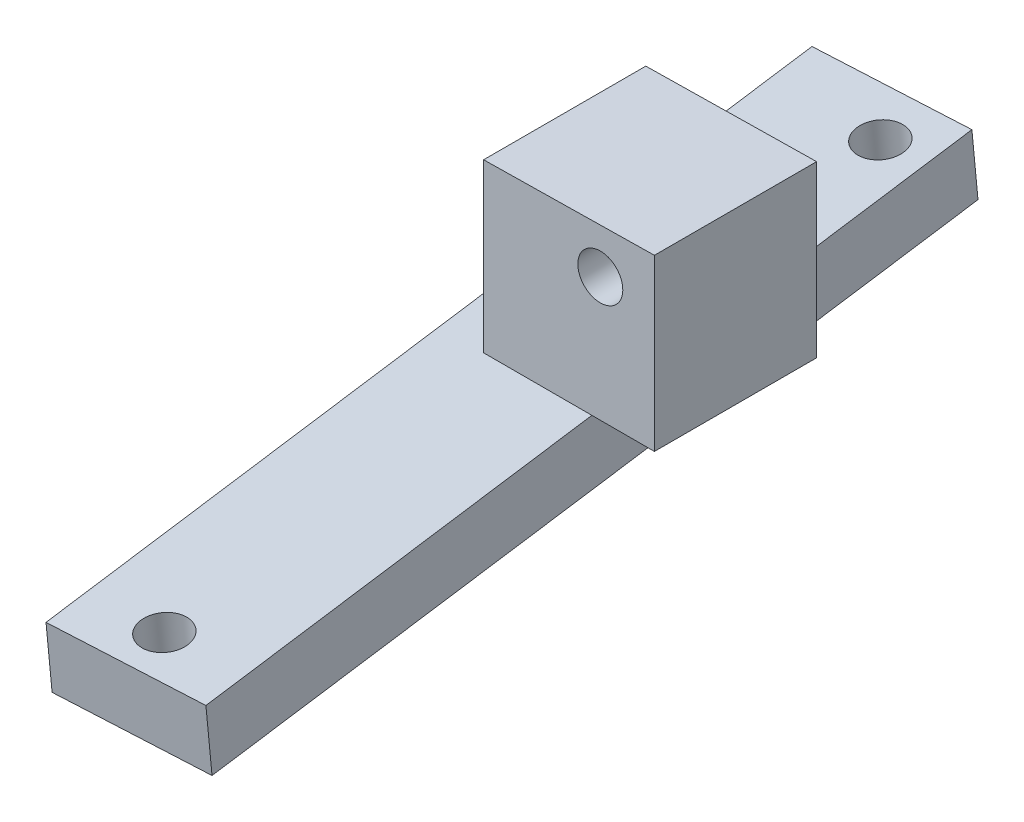
SolidWorks part; units mm, degrees
ref_plane "Front Plane" through (0, 0, 0) normal (0, 0, 1) x (1, 0, 0)
ref_plane "Top Plane" through (0, 0, 0) normal (0, 1, 0) x (1, 0, 0)
ref_plane "Right Plane" through (0, 0, 0) normal (1, 0, 0) x (0, 0, -1)
sketch "Sketch1" plane through (0, 0, 0) normal (0, 0, 1) x (1, 0, 0)
  line L4 (-277.3561, 264.2791) -> (-301.4861, 263.9)
  line L5 (-301.4861, 263.9) -> (-301.4861, 241.3438)
  line L6 (-301.4861, 241.3438) -> (-277.3561, 241.7228)
  line L7 (-277.3561, 241.7228) -> (-277.3561, 264.2791)
  circle A0 centre (-285, 257.8082) radius 3.175
  dimension "D6" = 6.35
  dimension "D1" = 3.81
  dimension "D2" = 3.81
  dimension "D3" = 24.13
  dimension "D4" = 22.5535
  dimension "D5" = 6.35
extrude "Boss-Extrude3" add sketch "Sketch1" along normal up to surface (22.9108 mm away) contours L7 L4 L5 L6 | A0
ref_plane "Plane1" through (0, 240.2331, 23.0373) normal (0, 0.9954, 0.0955) x (1, 0, 0)
sketch "Sketch2" plane through (0, 240.2331, 23.0373) normal (0, 0.9954, 0.0955) x (1, 0, 0)
  line L0 (-310.494, 55.7739) -> (-305.0454, -58.3962)
  line L1 (-305.0454, -58.3962) -> (-283.48, -57.367)
  line L2 (-283.48, -57.367) -> (-288.9285, 56.8031)
  line L3 (-288.9285, 56.8031) -> (-310.494, 55.7739)
  line L4 (-301.4861, 23.0381) -> (-277.3561, 23.0743) construction
  circle A0 centre (-294.8214, 49.7285) radius 3.175
  circle A1 centre (-294.8214, -51.8715) radius 3.175
  dimension "D9" = 6.35
  dimension "D10" = 6.35
  dimension "D1" = 87.354
  dimension "D2" = 21.59
  dimension "D3" = 6.35
  dimension "D4" = 58.3918
  dimension "D5" = 114.3
extrude "Boss-Extrude4" add sketch "Sketch2" against normal up to surface (9.0393 mm away)
sketch "Sketch5" plane through (0, 0, 22.9108) normal (0, 0, 1) x (1, 0, 0)
  line L0 (-301.4861, 241.3438) -> (-301.4861, 240.2807)
  line L1 (-301.4861, 240.2807) -> (-277.3561, 240.2807)
  line L2 (-277.3561, 240.2807) -> (-277.3561, 241.7228)
  line L3 (-277.3561, 241.7228) -> (-301.4861, 241.3438)
extrude "Boss-Extrude5" add sketch "Sketch5" against normal up to surface (22.9108 mm away) up to face at (-288.7208, 249.3921, 0)
